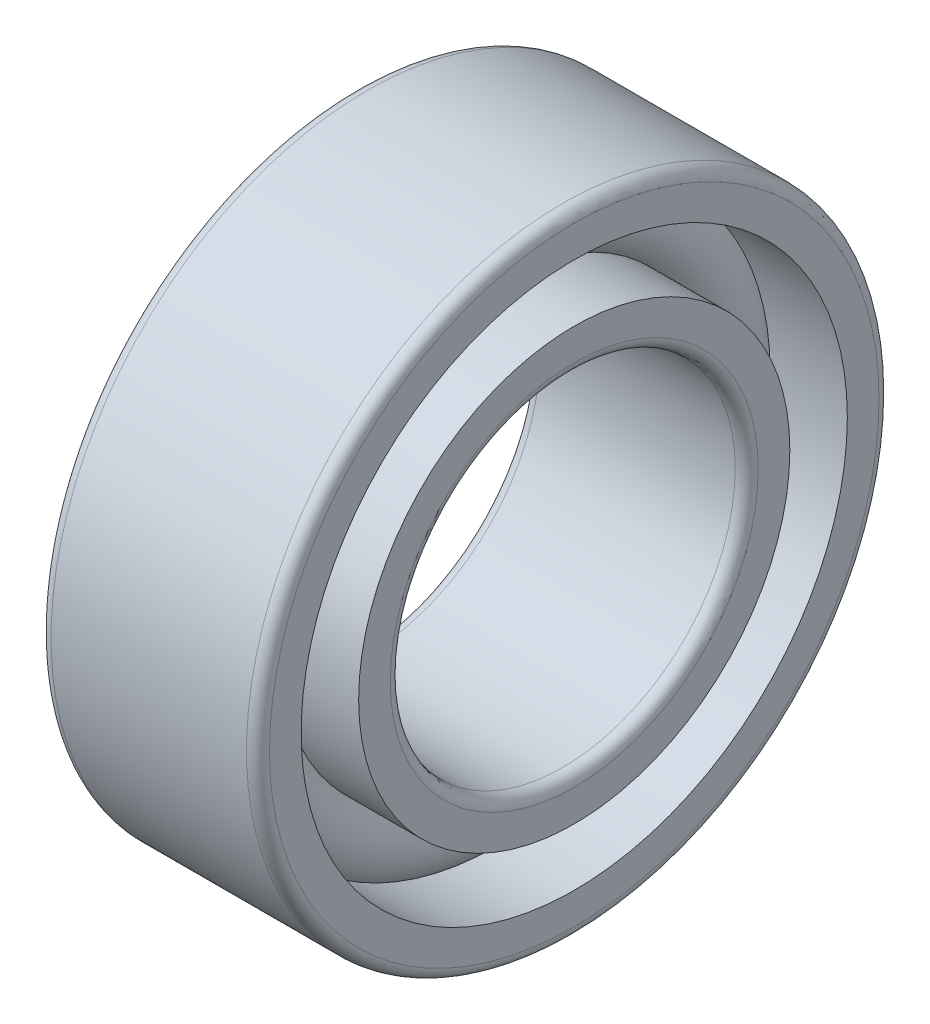
SolidWorks part; units mm, degrees
ref_plane "Plane1" through (0, 0, 0) normal (0, 0, 1) x (1, 0, 0)
ref_plane "Plane2" through (0, 0, 0) normal (0, 1, 0) x (1, 0, 0)
ref_plane "Plane3" through (0, 0, 0) normal (1, 0, 0) x (0, 0, -1)
other "Configuration Table"
sketch "Clipboard" plane through (0, 0, 0) normal (0, 0, 1) x (1, 0, 0)
  line L0 (-10, 0) -> (10, 0) construction
  line L1 (0, 0) -> (22.3471, -0.7804)
  line L2 (0, 0) -> (21.2371, 0.7416)
  line L3 (0, 0) -> (22.3471, -0.7804)
  line L4 (0, 0) -> (-22.3573, -0.3902)
sketch "CagSpiSke" plane through (0, 0, 0) normal (0, 0, 1) x (1, 0, 0)
  line L0 (0.375, 20.625) -> (0.375, 21.875)
  line L1 (0.375, 21.875) -> (-0.375, 21.875)
  line L2 (-0.375, 21.875) -> (-0.375, 20.625)
  line L3 (-0.375, 20.625) -> (0.375, 20.625)
  line L4 (-20.6375, 0) -> (20.6375, 0) construction
  line L5 (0, 0) -> (0, 23.7692) construction
revolve "CageSpine" add sketch "CagSpiSke" angle 0.001 about L4 reverse direction yes
ref_axis "Axis1" through (-50, 0, 0) along (1, 0, 0)
sketch "CagBalSke" plane through (0, 0, 0) normal (0, 0, 1) x (1, 0, 0)
  line L0 (-4.125, 21.25) -> (4.125, 21.25)
  line L1 (-1.905, 21.25) -> (1.905, 21.25) construction
  line L2 (-10, 0) -> (10, 0) construction
  line L3 (0, 0) -> (0, 24) construction
  arc A0 (4.125, 21.25) -> (-4.125, 21.25) centre (0, 21.25) cw
revolve "CageBall" [suppressed] add sketch "CagBalSke" angle 360 about L1 reverse direction yes
pattern_circular "CageBalls" [suppressed] count 2 every 180 about axis through (-50, 0, 0) along (1, 0, 0)
sketch "CagTrmODSke" plane through (0, 0, 0) normal (0, 0, 1) x (1, 0, 0)
  line L0 (4.126, 21.875) -> (4.126, 25.376)
  line L1 (4.126, 25.376) -> (-4.126, 25.376)
  line L2 (-4.126, 25.376) -> (-4.126, 21.875)
  line L3 (-4.126, 21.875) -> (4.126, 21.875)
  line L4 (-20.6375, 0) -> (20.6375, 0) construction
  line L5 (0, 0) -> (0, 25) construction
revolve "CageTrimOD" [suppressed] cut sketch "CagTrmODSke" angle 360 about L4 reverse direction yes
sketch "CagTrmIDSke" plane through (0, 0, 0) normal (0, 0, 1) x (1, 0, 0)
  line L0 (4.126, 17.126) -> (4.126, 20.625)
  line L1 (4.126, 20.625) -> (-4.126, 20.625)
  line L2 (-4.126, 20.625) -> (-4.126, 17.126)
  line L3 (-4.126, 17.126) -> (4.126, 17.126)
  line L4 (-20.6375, 0) -> (20.6375, 0) construction
  line L5 (0, 0) -> (0, 25) construction
revolve "CageTrimID" [suppressed] cut sketch "CagTrmIDSke" angle 360 about L4 reverse direction yes
sketch "BalSimSke" plane through (0, 0, 0) normal (0, 0, 1) x (1, 0, 0)
  line L0 (-10, 0) -> (10, 0) construction
  line L1 (-10, 21.25) -> (10, 21.25) construction
  line L2 (0, 0) -> (0, 23) construction
  circle A0 centre (0, 21.25) radius 3.75
revolve "BallsSimplified" add sketch "BalSimSke" angle 360 about L0
sketch "BalDetSke" plane through (0, 0, 0) normal (0, 0, 1) x (1, 0, 0)
  line L0 (-3.75, 21.25) -> (3.75, 21.25)
  line L1 (-1.905, 21.25) -> (1.905, 21.25) construction
  line L2 (0, 0) -> (0, 25) construction
  arc A0 (3.75, 21.25) -> (-3.75, 21.25) centre (0, 21.25) cw
revolve "BallDetailed" [suppressed] add sketch "BalDetSke" angle 360 about L1 reverse direction yes
sketch "InnRacSke" plane through (0, 0, 0) normal (0, 0, 1) x (1, 0, 0)
  line L0 (-2.7615, 18.75) -> (-9.5, 18.75)
  line L1 (-9.5, 18.75) -> (-9.5, 16)
  line L2 (-8.5, 15) -> (8.5, 15)
  line L3 (9.5, 16) -> (9.5, 18.75)
  line L4 (9.5, 18.75) -> (2.7615, 18.75)
  line L5 (-20.6375, 0) -> (20.6375, 0) construction
  line L6 (0, 0) -> (0, 30) construction
  arc A0 (-9.5, 16) -> (-8.5, 15) centre (-8.5, 16) ccw
  arc A1 (8.5, 15) -> (9.5, 16) centre (8.5, 16) ccw
  arc A2 (2.7615, 18.75) -> (-2.7615, 18.75) centre (0, 21.25) cw
revolve "InnerRace" add sketch "InnRacSke" angle 360 about L5 reverse direction yes
sketch "OutRacSke" plane through (0, 0, 0) normal (0, 0, 1) x (1, 0, 0)
  line L0 (-2.7615, 23.75) -> (-9.5, 23.75)
  line L1 (-9.5, 23.75) -> (-9.5, 26.5)
  line L2 (-8.5, 27.5) -> (8.5, 27.5)
  line L3 (9.5, 26.5) -> (9.5, 23.75)
  line L4 (9.5, 23.75) -> (2.7615, 23.75)
  line L5 (-20.6375, 0) -> (20.6375, 0) construction
  line L6 (0, 0) -> (0, 30) construction
  arc A0 (-9.5, 26.5) -> (-8.5, 27.5) centre (-8.5, 26.5) cw
  arc A1 (8.5, 27.5) -> (9.5, 26.5) centre (8.5, 26.5) cw
  arc A2 (2.7615, 23.75) -> (-2.7615, 23.75) centre (0, 21.25) ccw
revolve "OuterRace" add sketch "OutRacSke" angle 360 about L5 reverse direction yes
pattern_circular "BallsDetailed" [suppressed] count 2 every 180 about axis through (-50, 0, 0) along (1, 0, 0)
equation "\"BallCLRad@Clipboard\" = ( \"OD@OutRacSke\" + \"ID@InnRacSke\" ) / 4"
equation "\"BallCLRad@BalSimSke\" = \"BallCLRad@Clipboard\""
equation "\"BallCLRad@BalDetSke\" = \"BallCLRad@Clipboard\""
equation "\"BallCLRad@InnRacSke\" = \"BallCLRad@Clipboard\""
equation "\"BallCLRad@OutRacSke\" = \"BallCLRad@Clipboard\""
equation "\"Ball_diameter@InnRacSke\" = \"Ball_diameter@BalDetSke\" - 0.05"
equation "\"Ball_diameter@OutRacSke\" = \"Ball_diameter@BalDetSke\" - 0.05"
equation "\"Ball_diameter@BalSimSke\" = \"Ball_diameter@BalDetSke\""
equation "\"Width@OutRacSke\" = \"Width@InnRacSke\""
equation "\"Fillet_radius@OutRacSke\" = \"Fillet_radius@InnRacSke\""
equation "\"Max_count@Clipboard\" = int( 3.14159265 / atn(( \"Ball_diameter@BalDetSke\" / 2) / sqr( \"BallCLRad@Clipboard\"  *  \"BallCLRad@Clipboard\" - ( \"Ball_diameter@BalDetSke\" / 2) *  ( \"Ball_diameter@BalDetSke\" / 2))))"
equation "\"Max_count@Clipboard\" = ((sgn( \"Max_count@Clipboard\" - \"Count@Clipboard\" )-1)*( \"Max_count@Clipboard\" - \"Count@Clipboard\" ))/-2+ \"Count@Clipboard\""
equation "\"Count@BallsDetailed\" = int( \"Show_count@Clipboard\" ) "
equation "\"Count@BallsDetailed\" = ((sgn( \"Count@BallsDetailed\" - \"Max_count@Clipboard\" )-1)*( \"Count@BallsDetailed\" - \"Max_count@Clipboard\" ))/-2+ \"Max_count@Clipboard\""
equation "\"Count@BallsDetailed\" = ((sgn( \"Count@BallsDetailed\" - \"Min_count@Clipboard\" )+1)*( \"Count@BallsDetailed\" - \"Min_count@Clipboard\"))/2 +\"Min_count@Clipboard\""
equation "\"Angle@BallsDetailed\" = 360.0 / \"Max_count@Clipboard\""
equation "\"BallCLRad@CagBalSke\" = \"BallCLRad@Clipboard\""
equation "\"Count@CageBalls\" = \"Count@BallsDetailed\""
equation "\"Angle@CageBalls\" = \"Angle@BallsDetailed\""
equation "\"Angle@CageSpine\" =  \"Angle@CageBalls\" * ( \"Count@CageBalls\" -1 + int( \"Count@CageBalls\" / \"Max_count@Clipboard\" ) )  + 0.001 -  int( \"Count@CageBalls\" / \"Max_count@Clipboard\" ) * 0.001"
equation "\"Angle@CageSpine\" =  \"Angle@CageSpine\" * int( \"Min_count@Clipboard\" / 2) + int(1 / \"Min_count@Clipboard\")  * 0.001"
equation "\"CageWallOD@CagBalSke\" =  \"Ball_diameter@BalDetSke\" * 1.1"
equation "\"Thickness@CagSpiSke\" =  \"Ball_diameter@BalDetSke\" * 0.1"
equation "\"OD@CagTrmODSke\" = \"BallCLRad@Clipboard\" * 2 + \"CageWallOD@CagBalSke\" + 0.002"
equation "\"ID@CagTrmODSke\" = \"BallCLRad@Clipboard\" * 2 + \"Ball_diameter@BalDetSke\" / 6"
equation "\"OD@CagTrmIDSke\" = \"BallCLRad@Clipboard\" * 2 - \"Ball_diameter@BalDetSke\" / 6"
equation "\"ID@CagTrmIDSke\" = \"BallCLRad@Clipboard\" * 2 - \"CageWallOD@CagBalSke\" + 0.002"
equation "\"OD@CagSpiSke\" = \"ID@CagTrmODSke\""
equation "\"ID@CagSpiSke\" = \"OD@CagTrmIDSke\""
equation "\"Width@CagTrmODSke\" = \"CageWallOD@CagBalSke\" + 0.002"
equation "\"Width@CagTrmIDSke\" = \"CageWallOD@CagBalSke\" + 0.002"
